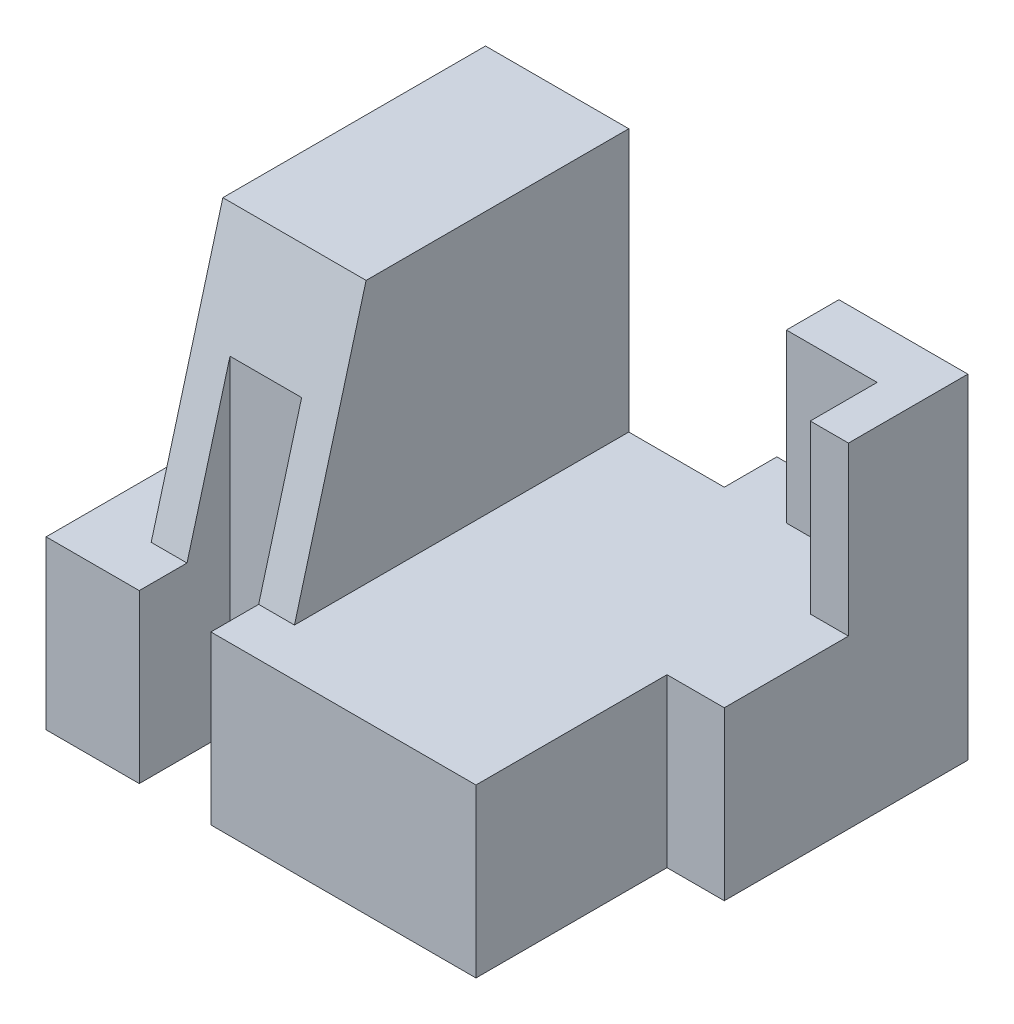
SolidWorks part; units mm, degrees
ref_plane "Спереди" through (0, 0, 0) normal (0, 0, 1) x (1, 0, 0)
ref_plane "Сверху" through (0, 0, 0) normal (0, 1, 0) x (1, 0, 0)
ref_plane "Справа" through (0, 0, 0) normal (1, 0, 0) x (0, 0, -1)
sketch "Эскиз1" plane through (0, 0, 0) normal (0, 0, 1) x (1, 0, 0)
  line L0 (30, -17.5) -> (45, 17.5)
  line L1 (-45, -17.5) -> (45, -17.5)
  line L2 (-45, -17.5) -> (-45, 17.5)
  line L3 (-45, 17.5) -> (45, 17.5)
  line L4 (45, -17.5) -> (45, 17.5)
  line L5 (-45, -17.5) -> (45, 17.5) construction
  line L6 (-45, 17.5) -> (45, -17.5) construction
  point P0 (0, 0)
  dimension "D1" = 35
  dimension "D2" = 90
  dimension "D3" = 15
extrude "Бобышка-Вытянуть1" add sketch "Эскиз1" along normal blind 80 contours L3 L2 L1 L0 region at (-3.6364, 0.5303, 0)
sketch "Эскиз2" plane through (-45, 0, 0) normal (-1, 0, 0) x (0, 0, 1)
  line L0 (0, 17.5) -> (0, 72.5)
  line L1 (0, 72.5) -> (55, 72.5)
  line L2 (55, 72.5) -> (70, 17.5)
  line L3 (80, 17.5) -> (0, 17.5) construction
  line L4 (70, 17.5) -> (0, 17.5)
  dimension "D1" = 55
  dimension "D2" = 70
  dimension "D3" = 55
extrude "Бобышка-Вытянуть2" add sketch "Эскиз2" against normal blind 30 from offset 12 offset against normal yes
sketch "Эскиз3" plane through (0, 72.5, 0) normal (0, 1, 0) x (1, 0, 0)
  line L0 (-18, 0) -> (-18, -80) construction
  line L1 (-3, 0) -> (-33, 0) construction
  line L2 (-45, -80) -> (45, -80) construction
  line L4 (-25.5, -61) -> (-10.5, -61)
  line L5 (-25.5, -61) -> (-25.5, -80)
  line L6 (-25.5, -80) -> (-10.5, -80)
  line L7 (-10.5, -61) -> (-10.5, -80)
  line L8 (-25.5, -61) -> (-10.5, -80) construction
  line L9 (-25.5, -80) -> (-10.5, -61) construction
  point P6 (-18, -70.5)
  dimension "D1" = 15
  dimension "D2" = 19
extrude "Вырез-Вытянуть1" cut sketch "Эскиз3" against normal through all
sketch "Эскиз4" plane through (0, 17.5, 0) normal (0, 1, 0) x (1, 0, 0)
  line L0 (-3, -55) -> (-3, 0) construction
  line L1 (17, -40) -> (57, -40)
  line L2 (17, -40) -> (17, 11)
  line L3 (17, 11) -> (57, 11)
  line L4 (57, -40) -> (57, 11)
  line L5 (17, -40) -> (57, 11) construction
  line L6 (17, 11) -> (57, -40) construction
  line L7 (-3, 0) -> (45, 0) construction
  line L8 (30, 11) -> (30, 0)
  line L9 (30, 0) -> (45, 0)
  line L10 (45, 0) -> (45, -14)
  line L11 (45, -80) -> (45, 0) construction
  line L12 (45, -14) -> (57, -14)
  point P0 (37, -14.5)
  line M4 (45, -80) -> (45, 0)
  line M5 (45, 0) -> (-3, 0)
  dimension "D1" = 20
  dimension "D2" = 40
  dimension "D3" = 40
  dimension "D4" = 11
  dimension "D5" = 27
  dimension "D6" = 25
extrude "Бобышка-Вытянуть3" add sketch "Эскиз4" against normal up to surface (35 mm away) contours L2 L1 M4 M5 | L12 L1 L4 M4 | L12 L4 L3 L8 M4 M5 | L8 L3 L2 M5 region at (31, 17.5, 20) region at (51, 17.5, 27) region at (23.5, 17.5, -5.5) region at (46.2097, 17.5, -0.9839) up to face at (-12.75, -17.5, 55.25)
extrude "Бобышка-Вытянуть4" add sketch "Эскиз4<3>" along normal blind 35 contours L12 L4 L3 L8 M4 M5 region at (46.2097, 17.5, -0.9839)
sketch "Эскиз4<3>" plane through (0, 17.5, 0) normal (0, 1, 0) x (1, 0, 0) same geometry as "Эскиз4"
sketch "Эскиз5" plane through (0, 52.5, 0) normal (0, 1, 0) x (1, 0, 0)
  line L0 (45, 0) -> (30, 0) construction
  line L1 (45, -14) -> (49, -14)
  line L2 (45, -14) -> (45, 0)
  line L3 (45, 0) -> (49, 0)
  line L4 (49, -14) -> (49, 0)
  line L6 (57, -14) -> (57, 11) construction
  dimension "D1" = 8
extrude "Вырез-Вытянуть2" cut sketch "Эскиз5" against normal up to surface (35 mm away) up to face at (-35.5, 17.5, 44.1667)
sketch "Эскиз6" plane through (0, 0, 80) normal (0, 0, 1) x (1, 0, 0)
  line L0 (30, -17.5) -> (45, 17.5)
  line L1 (45, 17.5) -> (45, -17.5)
  line L2 (57, -17.5) -> (30, -17.5) construction
  line L3 (45, -17.5) -> (30, -17.5)
extrude "Бобышка-Вытянуть5" add sketch "Эскиз6" against normal up to surface (40 mm away) up to face at (47.25, 0, 40)
